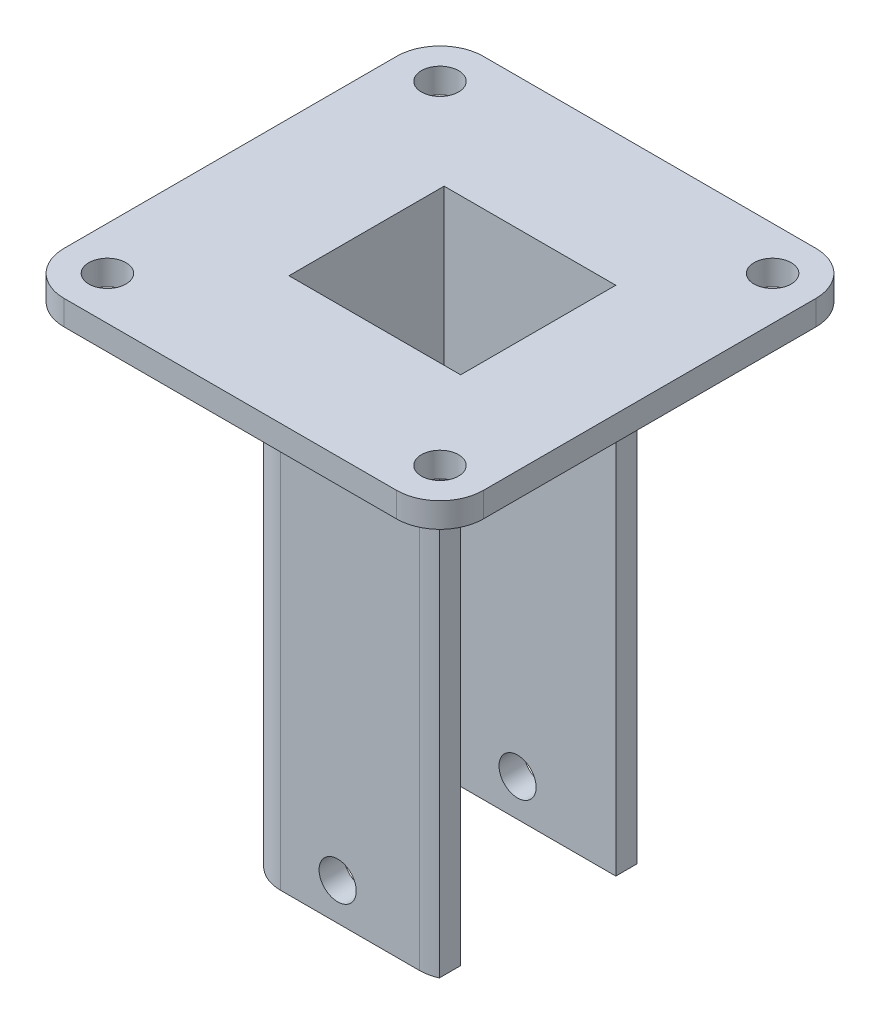
SolidWorks part; units mm, degrees
ref_plane "Front Plane" through (0, 0, 0) normal (0, 0, 1) x (1, 0, 0)
ref_plane "Top Plane" through (0, 0, 0) normal (0, 1, 0) x (1, 0, 0)
ref_plane "Right Plane" through (0, 0, 0) normal (1, 0, 0) x (0, 0, -1)
sketch "Sketch1" plane through (0, 0, 0) normal (0, 1, 0) x (1, 0, 0)
  line L0 (-57.93, -33) -> (48.39, -33)
  line L1 (-57.93, -33) -> (-57.93, 33)
  line L2 (48.39, -33) -> (48.39, 33)
  line L3 (-57.93, 33) -> (48.39, 33)
  line L6 (-6.4, 6.4) -> (6.4, 6.4)
  line L7 (-6.4, 6.4) -> (-6.4, -6.4)
  line L8 (6.4, 6.4) -> (6.4, -6.4)
  line L9 (-6.4, -6.4) -> (6.4, -6.4)
  point P1 (0, 0)
  dimension "D1" = 66
  dimension "D2" = 106.32
  dimension "D3" = 12.8
  dimension "D4" = 6.4
  dimension "D5" = 48.39
  dimension "D6" = 33
  dimension "D7" = 6.4
  dimension "D8" = 12.8
extrude "Boss-Extrude1" add sketch "Sketch1" along normal blind 3
sketch "Sketch2" plane through (0, 3, 0) normal (0, 1, 0) x (1, 0, 0)
  line L0 (-57.93, 33) -> (-57.93, -33) construction
  line L1 (48.39, 33) -> (-57.93, 33) construction
  line L2 (48.39, -33) -> (48.39, 33) construction
  line L3 (-57.93, -33) -> (48.39, -33) construction
  line L4 (-57.93, 33) -> (-57.93, 24)
  line L5 (48.39, 33) -> (39.39, 33)
  line L6 (48.39, -33) -> (48.39, -24)
  line L7 (-57.93, -33) -> (-48.93, -33)
  line L8 (-57.93, 24) -> (-48.93, 24)
  line L9 (-48.93, 24) -> (-48.93, 33)
  line L10 (39.39, 33) -> (39.39, 24)
  line L11 (39.39, 24) -> (48.39, 24)
  line L12 (-57.93, -24) -> (-48.93, -24)
  line L13 (-48.93, -24) -> (-48.93, -33)
  line L14 (-48.93, -33) -> (-48.93, -24)
  line L15 (39.39, -33) -> (39.39, -24)
  line L16 (39.39, -24) -> (48.39, -24)
  line L17 (-57.93, -24) -> (-57.93, -33)
  line L18 (-48.93, 33) -> (-57.93, 33)
  line L19 (39.39, -33) -> (48.39, -33)
  line L20 (48.39, 24) -> (48.39, 33)
  line M1 (-57.93, 33) -> (-57.93, -33)
  line M2 (-57.93, -33) -> (48.39, -33)
  line M3 (48.39, -33) -> (48.39, 33)
  line M4 (48.39, 33) -> (-57.93, 33)
  dimension "D1" = 9
  dimension "D2" = 9
  dimension "D3" = 9
  dimension "D4" = 9
  dimension "D5" = 9
  dimension "D6" = 9
  dimension "D7" = 9
  dimension "D8" = 9
extrude "Boss-Extrude2" [suppressed] add sketch "Sketch2" along normal blind 131 contours L8 L9 M4 M1 | L13 L12 M1 M2 | L16 L15 M2 M3 | L10 L11 M3 M4
sketch "Sketch3" plane through (0, 0, 0) normal (0, -1, 0) x (1, 0, 0)
  line L0 (-8.9, -9.4) -> (11.9, -9.4)
  line L1 (-8.9, -9.4) -> (-8.9, 9.4)
  line L2 (11.9, -9.4) -> (11.9, 9.4)
  line L3 (-8.9, 9.4) -> (11.9, 9.4)
  line L4 (-11.9, 12.4) -> (14.9, 12.4)
  line L5 (14.9, -12.4) -> (14.9, 12.4)
  line L6 (-11.9, -12.4) -> (14.9, -12.4)
  line L7 (-11.9, -12.4) -> (-11.9, 12.4)
  dimension "D1" = 8.9
  dimension "D2" = 20.8
  dimension "D3" = 18.8
  dimension "D4" = 9.4
  dimension "D5" = 3
extrude "Boss-Extrude3" add sketch "Sketch3" along normal blind 62
sketch "Sketch4" plane through (0, 0, -12.4) normal (0, 0, -1) x (-1, 0, 0)
  line L1 (11.9, 0) -> (-14.9, 0) construction
  circle A0 centre (0, -57.5) radius 2.25
  dimension "D1" = 57.5
  dimension "D2" = 4.5
extrude "Cut-Extrude3" cut sketch "Sketch4" against normal through all
fillet "Fillet1" [suppressed] radius 5
fillet "Fillet2" radius 5 4 edges at (-11.9, -31, 12.4) (14.9, -31, -12.4) (14.9, -31, 12.4) (-11.9, -31, -12.4)
sketch "Sketch6" [suppressed] plane through (0, 134, 0) normal (0, 1, 0) x (1, 0, 0)
  line L1 (-57.93, 33) -> (48.39, 33)
  line L2 (-57.93, 33) -> (-57.93, -33)
  line L3 (-57.93, -33) -> (48.39, -33)
  line L4 (48.39, 33) -> (48.39, -33)
extrude "Boss-Extrude4" [suppressed] add sketch "Sketch6" along normal blind 3
sketch "Sketch41" plane through (0, 0, 0) normal (0, -1, 0) x (1, 0, 0)
  line L0 (48.39, 33) -> (48.39, -33) construction
  line L1 (48.39, -33) -> (-57.93, -33) construction
  line L2 (-57.93, -33) -> (-57.93, 33) construction
  line L3 (-57.93, 33) -> (48.39, 33) construction
  line L4 (-6.9, -12.4) -> (9.9, -12.4)
  line L5 (-11.9, 7.4) -> (-11.9, -7.4)
  line L6 (9.9, 12.4) -> (-6.9, 12.4)
  line L7 (14.9, -7.4) -> (14.9, 7.4)
  line L8 (-6.9, -12.4) -> (9.9, -12.4)
  line L9 (-11.9, 7.4) -> (-11.9, -7.4)
  line L10 (9.9, 12.4) -> (-6.9, 12.4)
  line L11 (14.9, -7.4) -> (14.9, 7.4)
  line L12 (-6.9, -12.4) -> (9.9, -12.4) construction
  line L13 (48.39, 33) -> (48.39, -33)
  line L14 (48.39, -33) -> (-57.93, -33)
  line L15 (-57.93, -33) -> (-57.93, 33)
  line L16 (-57.93, 33) -> (48.39, 33)
  line L17 (-6.9, -12.4) -> (9.9, -12.4)
  arc A0 (-11.9, -7.4) -> (-6.9, -12.4) centre (-6.9, -7.4) ccw construction
  arc A1 (-11.9, -7.4) -> (-6.9, -12.4) centre (-6.9, -7.4) ccw
  arc A4 (-11.9, -7.4) -> (-6.9, -12.4) centre (-6.9, -7.4) ccw
  arc A5 (-6.9, 12.4) -> (-11.9, 7.4) centre (-6.9, 7.4) ccw
  arc A6 (14.9, 7.4) -> (9.9, 12.4) centre (9.9, 7.4) ccw
  arc A7 (9.9, -12.4) -> (14.9, -7.4) centre (9.9, -7.4) ccw
  arc A8 (-11.9, -7.4) -> (-6.9, -12.4) centre (-6.9, -7.4) ccw
  arc A9 (-6.9, 12.4) -> (-11.9, 7.4) centre (-6.9, 7.4) ccw
  arc A10 (14.9, 7.4) -> (9.9, 12.4) centre (9.9, 7.4) ccw
  arc A11 (9.9, -12.4) -> (14.9, -7.4) centre (9.9, -7.4) ccw
  line M9 (-57.93, 33) -> (-57.93, -33)
  line M10 (-57.93, -33) -> (48.39, -33)
  line M11 (48.39, -33) -> (48.39, 33)
  line M12 (48.39, 33) -> (-57.93, 33)
  line M13 (9.9, -12.4) -> (-6.9, -12.4)
  arc M14 (-6.9, -12.4) -> (-11.9, -7.4) centre (-6.9, -7.4) cw
  line M15 (-11.9, -7.4) -> (-11.9, 7.4)
  arc M16 (-11.9, 7.4) -> (-6.9, 12.4) centre (-6.9, 7.4) cw
  line M17 (-6.9, 12.4) -> (9.9, 12.4)
  arc M18 (9.9, 12.4) -> (14.9, 7.4) centre (9.9, 7.4) cw
  line M19 (14.9, 7.4) -> (14.9, -7.4)
  arc M20 (14.9, -7.4) -> (9.9, -12.4) centre (9.9, -7.4) cw
  dimension "D1" = 0
extrude "Boss-Extrude16" add sketch "Sketch41" along normal blind 3 contours M12 M9 M10 M11 M20 M13 M14 M15 M16 M17 M18 M19 region at (47.1386, 0, 0)
sketch "Sketch45" plane through (0, 3, 0) normal (0, 1, 0) x (1, 0, 0)
  line L4 (-57.93, 33) -> (-57.93, -33)
  line L5 (-57.93, -33) -> (48.39, -33)
  line L6 (48.39, -33) -> (48.39, 33)
  line L7 (48.39, 33) -> (-57.93, 33)
  line L8 (-57.93, 33) -> (-57.93, -33)
  line L9 (-57.93, -33) -> (48.39, -33)
  line L10 (48.39, -33) -> (48.39, 33)
  line L11 (48.39, 33) -> (-57.93, 33)
  dimension "D1" = 0
extrude "Cut-Extrude22" cut sketch "Sketch45" against normal blind 3
sketch "Sketch46" plane through (0, -3, 0) normal (0, -1, 0) x (1, 0, 0)
  line L0 (11.9, -9.4) -> (11.9, 9.4) construction
  line L1 (14.9, -7.4) -> (14.9, 7.4) construction
  line L2 (-6.9, -12.4) -> (9.9, -12.4) construction
  line L3 (9.9, 12.4) -> (-6.9, 12.4) construction
  line L4 (11.9, -12.4) -> (11.9, 12.4)
  line L5 (14.9, -12.4) -> (14.9, 12.4)
  line L6 (11.9, -12.4) -> (14.9, -12.4)
  line L7 (14.9, 12.4) -> (11.9, 12.4)
extrude "Cut-Extrude23" cut sketch "Sketch46" along normal through all
sketch "Sketch47" plane through (0, -3, 0) normal (0, -1, 0) x (-1, 0, 0)
  line L0 (-27.94, 0) -> (27.94, 0) construction
  line L1 (0, 27.94) -> (0, -27.94) construction
  line L2 (0, 0) -> (-8.6492, 0) construction
  line L3 (0, 0) -> (0, -4.5998) construction
  circle A0 centre (20.15, -20.15) radius 2.25
  circle A1 centre (20.15, 20.15) radius 2.25
  circle A2 centre (-20.15, -20.15) radius 2.25
  circle A3 centre (-20.15, 20.15) radius 2.25
  dimension "D1" = 4.5
  dimension "D2" = 20.15
  dimension "D3" = 20.15
extrude "Cut-Extrude25" cut sketch "Sketch47" against normal through all
sketch "Sketch49" plane through (0, -3, 0) normal (0, -1, 0) x (1, 0, 0)
  line L0 (-20.15, -25.4) -> (20.15, -25.4)
  line L1 (-25.4, -20.15) -> (-25.4, 20.15)
  line L2 (-20.15, 25.4) -> (20.15, 25.4)
  line L3 (25.4, -20.15) -> (25.4, 20.15)
  line L4 (-57.93, -33) -> (48.39, -33) construction
  line L5 (48.39, -33) -> (48.39, 33) construction
  line L6 (48.39, 33) -> (-57.93, 33) construction
  line L7 (-57.93, 33) -> (-57.93, -33) construction
  line L8 (-57.93, -33) -> (48.39, -33)
  line L9 (48.39, -33) -> (48.39, 33)
  line L10 (48.39, 33) -> (-57.93, 33)
  line L11 (-57.93, 33) -> (-57.93, -33)
  circle A24 centre (-20.15, -20.15) radius 5.25
  arc A25 (-25.4, -20.15) -> (-20.15, -25.4) centre (-20.15, -20.15) ccw
  circle A27 centre (20.15, -20.15) radius 5.25
  arc A28 (20.15, -25.4) -> (25.4, -20.15) centre (20.15, -20.15) ccw
  circle A30 centre (-20.15, 20.15) radius 5.25
  arc A31 (-20.15, 25.4) -> (-25.4, 20.15) centre (-20.15, 20.15) ccw
  circle A33 centre (20.15, 20.15) radius 5.25
  arc A34 (25.4, 20.15) -> (20.15, 25.4) centre (20.15, 20.15) ccw
  dimension "D1" = 3
  dimension "D2" = 3
  dimension "D3" = 3
  dimension "D4" = 3
extrude "Cut-Extrude26" cut sketch "Sketch49" against normal through all
fillet "Fillet9" radius 5 9 edges at (10.9215, -3, -12.2945) (1.5, -3, -12.4) (-10.4355, -3, -10.9355) (-11.9, -3, 0) (-10.4355, -3, 10.9355) (10.9215, -3, 12.2945) (11.9, -3, 10.6913) (11.9, -3, -10.6913) (1.5, -3, 12.4)
sketch "Sketch50" plane through (11.9, 0, 0) normal (-1, 0, 0) x (0, 0, 1)
  line L4 (-9.4, -3) -> (9.4, -3)
  line L5 (9.4, -3) -> (9.4, 0)
  line L6 (9.4, 0) -> (-9.4, 0)
  line L7 (-9.4, 0) -> (-9.4, -3)
  line L8 (-9.4, -3) -> (9.4, -3)
  line L9 (9.4, -3) -> (9.4, 0)
  line L10 (9.4, 0) -> (-9.4, 0)
  line L11 (-9.4, 0) -> (-9.4, -3)
  dimension "D1" = 0
extrude "Boss-Extrude17" [suppressed] add sketch "Sketch50" along normal blind 5.5
sketch "Sketch7" [suppressed] plane through (0, 137, 0) normal (0, 1, 0) x (1, 0, 0)
  line L0 (-48.93, -33) -> (39.39, -33) construction
  line L1 (48.39, -33) -> (48.39, 33) construction
  circle A0 centre (0, 0) radius 26.5
  dimension "D1" = 48.39
  dimension "D2" = 53
  dimension "D3" = 33
extrude "Cut-Extrude4" [suppressed] cut sketch "Sketch7" against normal blind 5
sketch "Sketch8" [suppressed] plane through (0, 134, 0) normal (0, -1, 0) x (1, 0, 0)
  line L0 (48.39, -24) -> (45.39, -24)
  line L1 (48.39, -24) -> (48.39, 24)
  line L2 (45.39, -24) -> (45.39, 24)
  line L3 (48.39, 24) -> (45.39, 24)
  line L4 (39.39, 24) -> (48.39, 24) construction
  dimension "D1" = 3
extrude "Boss-Extrude5" [suppressed] add sketch "Sketch8" along normal blind 131
sketch "Sketch10" [suppressed] plane through (0, 134, 0) normal (0, -1, 0) x (1, 0, 0)
  line L4 (0, 0) -> (14.8362, 0) construction
  circle A0 centre (25.3422, 22.8387) radius 1.625
  circle A1 centre (25.3422, -22.8387) radius 1.625
  circle A3 centre (0, 0) radius 26.5 construction
  circle A4 centre (0, 0) radius 26.5
  dimension "D4" = 3.25
  dimension "D5" = 34.115
extrude "Cut-Extrude6" [suppressed] cut sketch "Sketch10" against normal through all contours A0 | A1
sketch "Sketch21" [suppressed] plane through (0, 134, 0) normal (0, -1, 0) x (1, 0, 0)
  circle A0 centre (-33.93, 5.05) radius 1.625
  circle A1 centre (0, 0) radius 26.5 construction
  circle A2 centre (0, 0) radius 26.5
  dimension "D1" = 33.93
  dimension "D3" = 3.25
  dimension "D2" = 5.05
extrude "Cut-Extrude12" [suppressed] cut sketch "Sketch21" against normal up to next contours A0
sketch "Sketch11" [suppressed] plane through (0, 134, 0) normal (0, -1, 0) x (1, 0, 0)
  line L0 (-66, 44) -> (-47.7966, 14.3367) construction
  line L1 (-37.8467, 24.3295) -> (-35.4201, 26.404)
  line L2 (-45.5, 30) -> (-48.93, 47)
  line L5 (-45.5, 33) -> (-48.93, 33)
  line L8 (-48.93, 24) -> (-48.93, 33) construction
  line L9 (-48.93, 47) -> (-48.93, 33)
  line L11 (-45.7507, 11.0029) -> (-47.7966, 14.3367)
  line L12 (-51.4178, 12.7275) -> (-48.9912, 14.802)
  arc A3 (-37.8467, 24.3295) -> (-45.5, 30) centre (-45.5, 22) ccw
  arc A6 (-35.4201, 26.404) -> (-45.5, 33) centre (-45.5, 22) ccw
  arc A7 (-47.7966, 14.3367) -> (-48.9912, 14.802) centre (-45.5, 22) ccw
  circle A8 centre (-45.5, 22) radius 11 construction
  circle A9 centre (-45.5, 22) radius 8 construction
  arc A10 (-45.7507, 11.0029) -> (-51.4178, 12.7275) centre (-45.5, 22) ccw
  point P3 (-45.5, 22)
  point P4 (-23.505, 28.7245)
  point P5 (-23.505, 28.7245)
  point P8 (-27, 50)
  point P11 (-27, 45)
  point P16 (-17.5, 22)
  point P25 (-17.5, 22)
  dimension "D1" = 3
extrude "Boss-Extrude6" [suppressed] add sketch "Sketch11" along normal blind 12.2
sketch "Sketch12" [suppressed] plane through (0, 121.8, 0) normal (0, -1, 0) x (1, 0, 0)
  line L0 (-36.5645, -4.536) -> (-34.8232, -0.6054) construction
  line L1 (-45.5, 50) -> (-60, 50) construction
  line L2 (-36.5645, -4.536) -> (-19.842, 33.2102)
  line L3 (-45.5, 50) -> (-60, 50)
  line L5 (-60, 50) -> (-60, 47) construction
  line L6 (-60, 50) -> (-60, 44)
  line L7 (-66, 44) -> (-60, 44) construction
  line L8 (-47.3545, -2.9311) -> (-46.1381, -5.9927) construction
  line L10 (-66, 44) -> (-60, 44)
  line L11 (-66, 44) -> (-46.1381, -5.9927)
  arc A0 (-46.1381, -5.9927) -> (-36.5645, -4.536) centre (-45.5, 22) ccw construction
  arc A1 (-19.842, 33.2102) -> (-45.5, 50) centre (-45.5, 22) ccw construction
  arc A2 (-46.1381, -5.9927) -> (-36.5645, -4.536) centre (-45.5, 22) ccw
  arc A3 (-19.842, 33.2102) -> (-45.5, 50) centre (-45.5, 22) ccw
  point P9 (-56, 25.1613)
  point P12 (-61, 50)
  point P13 (-61, 25.1613)
  point P15 (-61, 35)
  point P16 (-56, 35)
extrude "Boss-Extrude7" [suppressed] add sketch "Sketch12" along normal blind 5
sketch "Sketch13" [suppressed] plane through (0, 116.8, 0) normal (0, -1, 0) x (1, 0, 0)
  line L2 (-66, 44) -> (-46.1381, -5.9927) construction
  line L3 (-59.8699, 28.5705) -> (-53.0906, 11.5068)
  arc A2 (-53.0906, 11.5068) -> (-59.8699, 28.5705) centre (-49.8906, 22.6567) ccw
  dimension "D1" = 23.2
extrude "Cut-Extrude7" [suppressed] cut sketch "Sketch13" against normal blind 2
sketch "Sketch14" [suppressed] plane through (0, 116.8, 0) normal (0, -1, 0) x (1, 0, 0)
  line L0 (-62.8216, 36) -> (-31.5, 36)
  line L1 (-45.5, 50) -> (-60, 50) construction
  line L2 (-66, 44) -> (-59.8699, 28.5705) construction
  line L3 (-66, 44) -> (-62.8216, 36)
  line L4 (-59.8164, 36) -> (-31.5, 36) construction
  line L5 (-60.7854, 39) -> (-62.7719, 44)
  line L6 (-31.5, 8) -> (-31.5, 36)
  line L7 (-66, -44) -> (-66, 44) construction
  line L8 (-36.5645, -4.536) -> (-19.842, 33.2102) construction
  line L9 (-53.0906, 11.5068) -> (-46.1381, -5.9927) construction
  line L10 (-28.5, 13.6674) -> (-28.5, 39)
  line L11 (-60.7854, 39) -> (-28.5, 39)
  line L12 (-59.8164, 39) -> (-28.5, 39) construction
  line L13 (-28.5, 6.8958) -> (-28.5, 39) construction
  line L14 (-31.5, 8) -> (-51.6974, 8)
  line L15 (-51.6974, 8) -> (-50.5055, 5)
  line L17 (-32.3399, 5) -> (-28.5, 13.6674)
  line L18 (-31.0108, 8) -> (-50.9566, 8) construction
  line L19 (-32.3399, 5) -> (-50.5055, 5)
  line L20 (-31.5, 6.8958) -> (-28.5, 13.6674)
  line L21 (-31.0108, 5) -> (-50.9566, 5) construction
  line L22 (-31.5, 6.8958) -> (-31.5, 36) construction
  line L23 (-60, 44) -> (-66, 44) construction
  line L24 (-62.7719, 44) -> (-66, 44)
  point P16 (-59, 42)
  point P17 (-56, 40)
  dimension "D1" = 14
  dimension "D2" = 34.5
  dimension "D3" = 3
  dimension "D4" = 42
  dimension "D6" = 3
  dimension "D5" = 3
extrude "Boss-Extrude8" [suppressed] add sketch "Sketch14" along normal blind 24
sketch "Sketch29" [suppressed] plane through (0, 134, 0) normal (0, -1, 0) x (1, 0, 0)
  line L1 (-57.93, -24) -> (-57.93, 24) construction
  line L4 (-48.93, 24) -> (-48.93, 27)
  line L5 (-48.93, 24) -> (-48.93, 33) construction
  line L6 (-57.93, 2) -> (-41.93, 2)
  line L7 (-57.93, 5) -> (-41.93, 5)
  line L8 (-48.93, 24) -> (-41.93, 24)
  line L9 (-48.93, 27) -> (-41.93, 27)
  line L14 (-57.93, 2) -> (-57.93, 5)
  arc A0 (-41.93, 2) -> (-41.93, 27) centre (-41.93, 14.5) ccw
  arc A1 (-41.93, 5) -> (-41.93, 24) centre (-41.93, 14.5) ccw
  circle A3 centre (-41.93, 14.5) radius 12.5 construction
  circle A4 centre (-41.93, 14.5) radius 9.5 construction
  point P1 (-32.2829, 11.5)
  point P15 (-29.8291, 15.1546)
  dimension "D1" = 25
  dimension "D3" = 3
  dimension "D4" = 16
extrude "Boss-Extrude12" [suppressed] add sketch "Sketch29" along normal blind 11.3 contours L14 L7 A1 L8 L4 L9 A0 L6
sketch "Sketch25" [suppressed] plane through (0, 122.7, 0) normal (0, -1, 0) x (1, 0, 0)
  line L2 (-57.93, 24) -> (-41.93, 24) construction
  line L3 (-57.93, 5) -> (-57.93, 24) construction
  line L4 (-57.93, 5) -> (-57.93, 24)
  line L6 (-57.93, 5) -> (-41.93, 5) construction
  line L7 (-57.93, 24) -> (-41.93, 24)
  line L8 (-57.93, 5) -> (-41.93, 5)
  arc A0 (-41.93, 5) -> (-41.93, 24) centre (-41.93, 14.5) ccw construction
  arc A1 (-41.93, 5) -> (-41.93, 24) centre (-41.93, 14.5) ccw
  circle A2 centre (-41.93, 14.5) radius 3.9
  point P13 (-42.4424, 11.9931)
  point P14 (-32.8261, 23.4534)
  point P15 (-48.4176, 17.0069)
  point P16 (-38.8013, 28.4671)
  dimension "D1" = 7.8
extrude "Boss-Extrude11" [suppressed] add sketch "Sketch25" against normal blind 3
sketch "Sketch32" [suppressed] plane through (0, 137, 0) normal (0, 1, 0) x (1, 0, 0)
  line L6 (-42.2096, -2.5625) -> (-42.2096, 0.578) construction
  line L7 (-48.5223, 1) -> (-45.43, 1) construction
  line L8 (-48.5223, -2) -> (-48.5223, 1) construction
  line L9 (-42.2096, -20.4375) -> (-42.2096, -23.578) construction
  line L10 (-48.5223, -24) -> (-45.43, -24) construction
  line L11 (-48.5223, -21) -> (-48.5223, -24) construction
  line L13 (-42.2096, -2.5625) -> (-42.2096, 0.578)
  line L14 (-48.5223, 1) -> (-45.43, 1)
  line L15 (-48.5223, -2) -> (-48.5223, 1)
  line L16 (-42.2096, -20.4375) -> (-42.2096, -23.578)
  line L17 (-48.5223, -24) -> (-45.43, -24)
  line L18 (-48.5223, -21) -> (-48.5223, -24)
  arc A2 (-42.2096, 0.578) -> (-45.43, 1) centre (-45.43, -11.5) ccw construction
  arc A3 (-45.43, -24) -> (-42.2096, -23.578) centre (-45.43, -11.5) ccw construction
  arc A6 (-42.2096, 0.578) -> (-45.43, 1) centre (-45.43, -11.5) ccw
  arc A7 (-45.43, -24) -> (-42.2096, -23.578) centre (-45.43, -11.5) ccw
  arc A8 (-48.5223, -21) -> (-42.2096, -20.4375) centre (-45.43, -20) ccw
  arc A9 (-42.2096, -2.5625) -> (-48.5223, -2) centre (-45.43, -3) ccw
  dimension "D1" = 6.5
sketch "Sketch37" [suppressed] plane through (0, 125.7, 0) normal (0, 1, 0) x (1, 0, 0)
  line L0 (-57.93, -5) -> (-57.93, -24) construction
  line L1 (-41.93, -5) -> (-57.93, -5) construction
  line L2 (-57.93, -24) -> (-41.93, -24) construction
  line L3 (-57.93, -5) -> (-57.93, -24)
  line L4 (-41.93, -5) -> (-57.93, -5)
  line L5 (-57.93, -24) -> (-41.93, -24)
  line L6 (-32.9925, -17.7204) -> (-29.852, -17.7204)
  line L7 (-32.9925, -11.2796) -> (-29.852, -11.2796)
  arc A0 (-41.93, -24) -> (-41.93, -5) centre (-41.93, -14.5) ccw construction
  arc A1 (-41.93, -24) -> (-32.9925, -17.7204) centre (-41.93, -14.5) ccw
  arc A5 (-32.9925, -11.2796) -> (-41.93, -5) centre (-41.93, -14.5) ccw
  arc A6 (-29.852, -17.7204) -> (-29.852, -11.2796) centre (-41.93, -14.5) ccw
  dimension "D3" = 25
extrude "Cut-Extrude20" [suppressed] cut sketch "Sketch37" along normal up to surface (11.3 mm away) contours A5 L4 L3 L5 A1 L6 A6 L7 up to face at (5.0016, -3, 0)
sketch "Sketch38" [suppressed] plane through (0, 125.7, 0) normal (0, 1, 0) x (1, 0, 0)
  circle A0 centre (-33.43, -14.3622) radius 1.9875
  circle A1 centre (-50.43, -14.3622) radius 1.9875
  circle A2 centre (-41.93, -14.5) radius 3.9 construction
  dimension "D1" = 3.975
  dimension "D2" = 3.975
  dimension "D3" = 17
  dimension "D4" = 8.5
extrude "Cut-Extrude21" [suppressed] cut sketch "Sketch38" against normal up to surface (3 mm away) up to face at (5.0016, -3, 0)
extrude "Boss-Extrude13" [suppressed] add sketch "Sketch32" against normal up to surface (3 mm away) up to face at (5.0016, -3, 0)
sketch "Sketch36" [suppressed] plane through (0, 134, 0) normal (0, -1, 0) x (1, 0, 0)
  circle A10 centre (-33.93, 5.05) radius 8
  circle A11 centre (-33.93, 5.05) radius 8
  dimension "D3" = 6.375
extrude "Cut-Extrude19" [suppressed] cut sketch "Sketch36" along normal up to surface (8.3 mm away) contours A11 up to face at (5.0016, -3, 0)
fillet "Fillet3" [suppressed] radius 2
fillet "Fillet4" [suppressed] radius 5
chamfer "Chamfer1" [suppressed] distance 4 angle 45
fillet "Fillet5" [suppressed] radius 0.8
sketch "Sketch16" [suppressed] plane through (0, 134, 0) normal (0, -1, 0) x (1, 0, 0)
  line L2 (-57.93, -24) -> (-57.93, 2) construction
  line L4 (-48.93, 33) -> (39.39, 33) construction
  line L5 (39.39, -33) -> (-48.93, -33) construction
  circle A0 centre (-23.67, -26) radius 1.6
  circle A1 centre (16.33, -26) radius 1.6
  circle A4 centre (16.33, 26) radius 1.6
  circle A5 centre (-23.67, 26) radius 1.6
  dimension "D4" = 3.2
  dimension "D2" = 7
  dimension "D1" = 7
  dimension "D3" = 40
  dimension "D5" = 34.26
extrude "Cut-Extrude13" [suppressed] cut sketch "Sketch16" against normal blind 10
sketch "Sketch22" [suppressed] plane through (0, 137, 0) normal (0, 1, 0) x (1, 0, 0)
  line L0 (0, 0) -> (18.4844, 0) construction
  line L1 (48.39, -28.6686) -> (48.39, 28.6686) construction
  line L2 (-57.93, 28.6686) -> (-57.93, -5) construction
  circle A0 centre (40.555, 0) radius 2.375
  circle A1 centre (-50.095, 0) radius 2.375
  dimension "D1" = 4.75
  dimension "D4" = 4.75
  dimension "D2" = 7.835
  dimension "D3" = 7.835
extrude "Cut-Extrude14" [suppressed] cut sketch "Sketch22" against normal up to surface (11.3 mm away) up to face at (5.0016, -3, 0)
sketch "Sketch34" [suppressed] plane through (0, 134, 0) normal (0, -1, 0) x (1, 0, 0)
  line L0 (-45.3294, -4.7656) -> (-45.3294, 7.2344)
  line L1 (-54.8606, 7.2344) -> (-54.8606, -4.7656)
  line L2 (-50.095, -11.5275) -> (-50.095, -0.8064) construction
  line L3 (-50.095, 0) -> (-48.5122, 0) construction
  line L4 (-54.8606, 7.2344) -> (-45.3294, 7.2344)
  line L5 (-45.3294, -4.7656) -> (-54.8606, -4.7656)
  arc A0 (-51.3759, 2) -> (-48.8141, 2) centre (-50.095, 0) ccw construction
  dimension "D5" = 4.7656
  dimension "D1" = 9.5312
  dimension "D2" = 4.7656
  dimension "D3" = 0
  dimension "D4" = 12
extrude "Cut-Extrude18" [suppressed] cut sketch "Sketch34" along normal up to surface (8.3 mm away) up to face at (5.0016, -3, 0)
sketch "Sketch17" [suppressed] plane through (0, 134, 0) normal (0, -1, 0) x (1, 0, 0)
  line L0 (48.39, 28.6686) -> (48.39, -28.6686) construction
  line L1 (42.39, 11) -> (38.39, 11)
  line L2 (42.39, 11) -> (42.39, -11)
  line L3 (42.39, -11) -> (38.39, -11)
  line L4 (38.39, 11) -> (38.39, -11)
  circle A0 centre (0, 0) radius 26.5 construction
  dimension "D1" = 22
  dimension "D2" = 4
  dimension "D3" = 11
  dimension "D4" = 10
extrude "Cut-Extrude9" [suppressed] cut sketch "Sketch17" against normal up to next
sketch "Sketch18" [suppressed] plane through (0, 134, 0) normal (0, -1, 0) x (1, 0, 0)
  line L0 (-57.93, -24) -> (-57.93, 2) construction
  line L1 (-49.93, -5.5) -> (-54.93, -5.5)
  line L2 (-49.93, -5.5) -> (-49.93, -11)
  line L3 (-49.93, -11) -> (-54.93, -11)
  line L4 (-54.93, -5.5) -> (-54.93, -11)
  circle A0 centre (0, 0) radius 26.5 construction
  dimension "D1" = 5.5
  dimension "D2" = 5
  dimension "D3" = 11
  dimension "D4" = 3
extrude "Cut-Extrude10" [suppressed] cut sketch "Sketch18" against normal up to next
sketch "Sketch19" [suppressed] plane through (0, 137, 0) normal (0, 1, 0) x (1, 0, 0)
  line L0 (44.0586, 33) -> (-53.5986, 33) construction
  line L1 (-24.15, 33) -> (-18, 33)
  line L2 (-24.15, 33) -> (-24.15, 26.85)
  line L3 (-24.15, 26.85) -> (-18, 26.85)
  line L4 (-18, 33) -> (-18, 26.85)
  line L5 (-53.5986, -33) -> (44.0586, -33) construction
  line L6 (18, 33) -> (24.15, 33)
  line L7 (18, 33) -> (18, 26.85)
  line L8 (18, 26.85) -> (24.15, 26.85)
  line L9 (24.15, 33) -> (24.15, 26.85)
  line L10 (-24.15, -33) -> (-18, -33)
  line L11 (-24.15, -33) -> (-24.15, -26.85)
  line L12 (-24.15, -26.85) -> (-18, -26.85)
  line L13 (-18, -33) -> (-18, -26.85)
  line L14 (-57.93, 28.6686) -> (-57.93, -5) construction
  line L15 (18, -33) -> (24.15, -33)
  line L16 (18, -33) -> (18, -26.85)
  line L17 (18, -26.85) -> (24.15, -26.85)
  line L18 (24.15, -33) -> (24.15, -26.85)
  circle A0 centre (0, 0) radius 26.5 construction
  dimension "D1" = 6.15
  dimension "D2" = 36
  dimension "D3" = 18
  dimension "D4" = 33.78
extrude "Cut-Extrude11" [suppressed] cut sketch "Sketch19" against normal up to next
sketch "Sketch33" [suppressed] plane through (0, 122.7, 0) normal (0, -1, 0) x (-1, 0, 0)
  circle A0 centre (45.43, -11.5) radius 12.5
sketch "Sketch39" [suppressed] plane through (0, 134, 0) normal (0, -1, 0) x (1, 0, 0)
  line L0 (-48.93, 33) -> (39.39, 33) construction
  line L1 (-48.93, 27) -> (-48.93, 33) construction
  line L2 (-48.93, 27) -> (-41.93, 27) construction
  line L3 (-48.93, 33) -> (-23.93, 33)
  line L4 (-48.93, 27) -> (-48.93, 33)
  line L5 (-48.93, 27) -> (-23.93, 27)
  line L6 (-23.93, 27) -> (-23.93, 33)
  dimension "D1" = 25
extrude "Boss-Extrude14" [suppressed] add sketch "Sketch39" along normal blind 35
sketch "Sketch40" [suppressed] plane through (0, 134, 0) normal (0, -1, 0) x (1, 0, 0)
  line L0 (-41.93, 27) -> (-23.93, 27) construction
  line L1 (-41.93, 27) -> (-29.852, 27)
  line L2 (-29.852, 17.7204) -> (-29.852, 27)
  arc A0 (-29.852, 17.7204) -> (-41.93, 27) centre (-41.93, 14.5) ccw construction
  arc A1 (-29.852, 17.7204) -> (-41.93, 27) centre (-41.93, 14.5) ccw
extrude "Boss-Extrude15" [suppressed] add sketch "Sketch40" along normal up to surface (11.3 mm away) up to face at (5.0016, -3, 0)
fillet "Fillet6" [suppressed] radius 0.8
fillet "Fillet7" [suppressed] radius 0.8
fillet "Fillet8" [suppressed] radius 0.8
